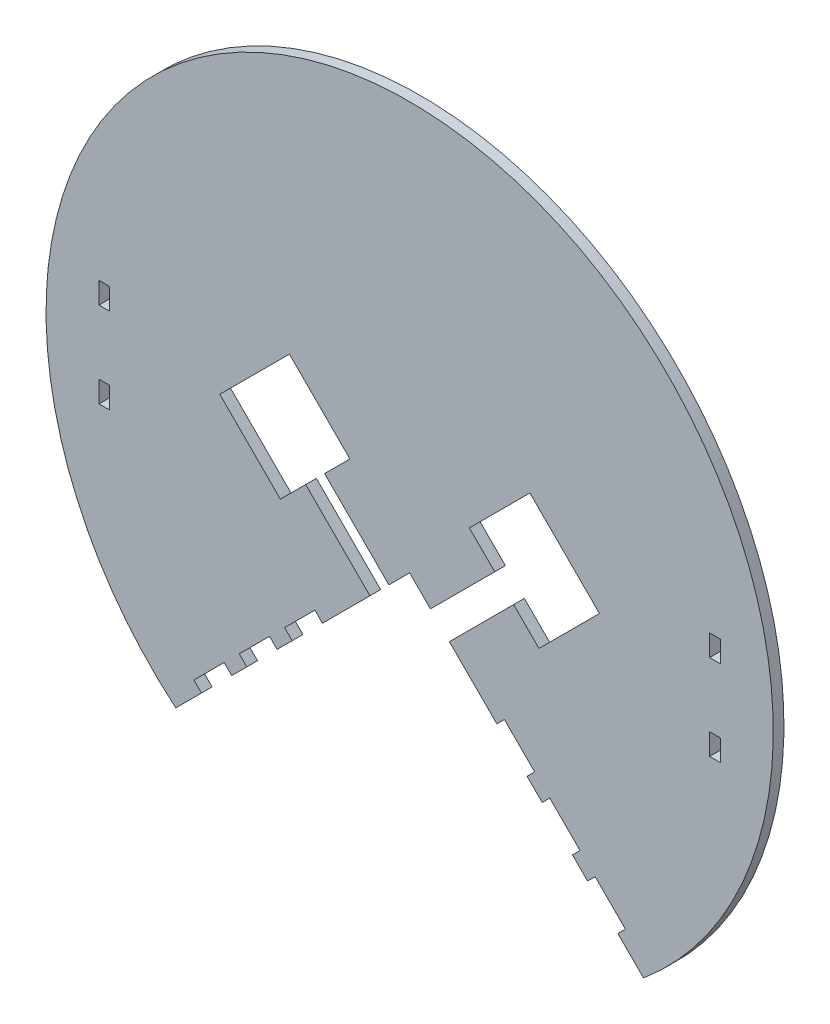
SolidWorks part; units mm, degrees
ref_plane "Front Plane" through (0, 0, 0) normal (0, 0, 1) x (1, 0, 0)
ref_plane "Top Plane" through (0, 0, 0) normal (0, 1, 0) x (1, 0, 0)
ref_plane "Right Plane" through (0, 0, 0) normal (1, 0, 0) x (0, 0, -1)
sketch "Sketch1" plane through (0, 0, 0) normal (0, 0, 1) x (1, 0, 0)
  circle A0 centre (0, 0) radius 215.9
  arc A1 (209.8384, 50.8) -> (-209.8384, 50.8) centre (0, 0) ccw construction
extrude "Boss-Extrude1" add sketch "Sketch1" along normal blind 6.35 contours A0
sketch "Sketch2" plane through (0, 0, 0) normal (0, 0, -1) x (-1, 0, 0)
  line L0 (0, -26.4411) -> (138.8703, -165.3114)
  line L2 (0, -26.4411) -> (-138.8703, -165.3114)
  line L3 (-139.4438, -165.8849) -> (-121.2335, -147.6746) construction
  line L4 (0, 0) -> (0, -240.5018) construction
  arc A4 (-138.8703, -165.3114) -> (138.8703, -165.3114) centre (0, 0) ccw
  circle A5 centre (0, 0) radius 215.9 construction
  dimension "D1" = 90
extrude "Cut-Extrude1" cut sketch "Sketch2" against normal through all
sketch "Sketch3" plane through (0, 0, 6.35) normal (0, 0, 1) x (1, 0, 0)
  line L0 (71.393, 50.3401) -> (112.7022, 9.0309)
  line L1 (71.393, 50.3401) -> (35.472, 14.4191)
  line L2 (112.7022, 9.0309) -> (76.7812, -26.8901)
  line L3 (35.472, 14.4191) -> (76.7812, -26.8901)
  line L4 (76.7812, -26.8901) -> (72.2911, -22.4) construction
  line L5 (97.2507, 34.8885) -> (46.1575, -16.2046) construction
  line L6 (50.5139, -0.6229) -> (61.7393, -11.8482)
  line L7 (50.5139, -0.6229) -> (12.3479, -38.7889)
  line L8 (61.7393, -11.8482) -> (23.5732, -50.0143)
  line L9 (12.3479, -38.7889) -> (23.5732, -50.0143)
  line L10 (88.68, 15.0926) -> (77.4547, 26.3179) construction
  line L11 (0, -26.4411) -> (138.8703, -165.3114) construction
  line M8 (0, -26.4411) -> (138.8703, -165.3114)
extrude "Cut-Extrude2" cut sketch "Sketch3" against normal through all contours L8 L6 L3 L7 M8 | L0 L5 L6 L3 L2 | L5 L0 L1 L3 region at (63.7598, 22.0523, 6.35) region at (84.4144, 1.3977, 6.35) region at (37.0436, -25.3186, 6.35)
mirror "Mirror1" about plane through (0, 0, 0) normal (1, 0, 0) of "Cut-Extrude2"
sketch "Sketch4" plane through (0, 0, 6.35) normal (0, 0, 1) x (1, 0, 0)
  line L0 (-178.0884, 19.05) -> (-178.0884, 31.75) construction
  line L1 (178.0884, -19.05) -> (184.4384, -19.05)
  line L2 (178.0884, -19.05) -> (178.0884, -31.75)
  line L3 (178.0884, -31.75) -> (184.4384, -31.75)
  line L4 (184.4384, -19.05) -> (184.4384, -31.75)
  line L5 (178.0884, 31.75) -> (184.4384, 31.75)
  line L6 (178.0884, 31.75) -> (178.0884, 19.05)
  line L7 (178.0884, 19.05) -> (184.4384, 19.05)
  line L8 (184.4384, 31.75) -> (184.4384, 19.05)
  line L9 (178.0884, -19.05) -> (184.4384, -19.05)
  line L10 (178.0884, -19.05) -> (178.0884, -31.75)
  line L11 (178.0884, -31.75) -> (184.4384, -31.75)
  line L12 (184.4384, -19.05) -> (184.4384, -31.75)
  line L13 (-184.4384, 31.75) -> (-178.0884, 31.75)
  line L14 (-184.4384, 31.75) -> (-184.4384, 19.05)
  line L15 (-184.4384, 19.05) -> (-178.0884, 19.05)
  line L16 (-178.0884, 31.75) -> (-178.0884, 19.05)
  line L18 (-184.4384, -19.05) -> (-178.0884, -19.05)
  line L19 (-184.4384, -19.05) -> (-184.4384, -31.75)
  line L20 (-184.4384, -31.75) -> (-178.0884, -31.75)
  line L21 (-178.0884, -19.05) -> (-178.0884, -31.75)
extrude "Cut-Extrude3" cut sketch "Sketch4" against normal through all contours L21 L18 L19 L20 | L8 L5 L6 L7 | L4 L1 L2 L3 | L14 L15 L16 L13 region at (181.2634, -25.4, 6.35) region at (181.2634, 25.4, 6.35) region at (-181.2634, -25.4, 6.35)
sketch "Sketch5" plane through (0, 0, 6.35) normal (0, 0, 1) x (1, 0, 0)
  line L0 (-128.1057, -145.5666) -> (-110.1452, -127.6061)
  line L1 (-110.1452, -127.6061) -> (-105.6551, -132.0962)
  line L2 (-138.8703, -165.3114) -> (-23.5732, -50.0143) construction
  line L3 (-105.6551, -132.0962) -> (-110.1452, -127.6061) construction
  line L4 (-105.6551, -132.0962) -> (-123.6156, -150.0567)
  line L5 (-128.1057, -145.5666) -> (-123.6156, -150.0567) construction
  line L6 (-123.6156, -150.0567) -> (-128.1057, -145.5666)
extrude "Cut-Extrude4" cut sketch "Sketch5" against normal blind 6.35
pattern_linear "LPattern1" count 3 spacing 38.1 along (0.7071, 0.7071, 0) of "Cut-Extrude4"
sketch "Sketch6" plane through (0, 0, 6.35) normal (0, 0, 1) x (1, 0, 0)
  line L0 (110.1452, -127.6061) -> (128.1057, -145.5666)
  line L1 (128.1057, -145.5666) -> (123.6156, -150.0567)
  line L2 (23.5732, -50.0143) -> (138.8703, -165.3114) construction
  line L3 (123.6156, -150.0567) -> (128.1057, -145.5666) construction
  line L4 (123.6156, -150.0567) -> (105.6551, -132.0962)
  line L5 (110.1452, -127.6061) -> (105.6551, -132.0962) construction
  line L6 (105.6551, -132.0962) -> (110.1452, -127.6061)
extrude "Cut-Extrude5" cut sketch "Sketch6" against normal blind 6.35
pattern_linear "LPattern2" count 3 spacing 38.1 along (-0.7071, 0.7071, 0) of "Cut-Extrude5"
